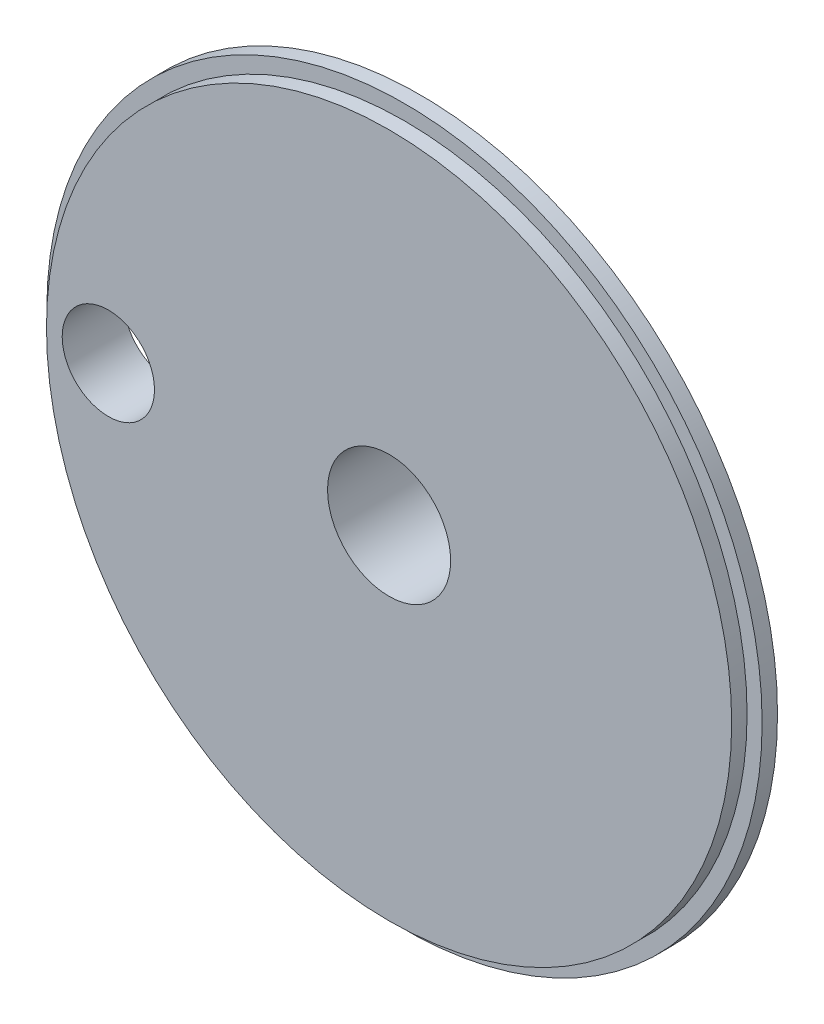
SolidWorks part; units mm, degrees
ref_plane "Front Plane" through (0, 0, 0) normal (0, 0, 1) x (1, 0, 0)
ref_plane "Top Plane" through (0, 0, 0) normal (0, 1, 0) x (1, 0, 0)
ref_plane "Right Plane" through (0, 0, 0) normal (1, 0, 0) x (0, 0, -1)
sketch "Sketch7" plane through (0, 0, 0) normal (0, 0, 1) x (1, 0, 0)
  circle A0 centre (0, 0) radius 46.5
  circle A2 centre (0, 0) radius 8
  circle A3 centre (-36.5, 0) radius 6
  dimension "D1" = 16
  dimension "D2" = 12
  dimension "D3" = 93
  dimension "D4" = 36.5
extrude "Boss-Extrude9" add sketch "Sketch7" along normal blind 2
sketch "Sketch8" plane through (0, 0, 2) normal (0, 0, 1) x (1, 0, 0)
  circle A0 centre (0, 0) radius 44.5424
  circle A1 centre (0, 0) radius 8 construction
  circle A2 centre (-36.5, 0) radius 6 construction
  circle A3 centre (0, 0) radius 8
  circle A4 centre (-36.5, 0) radius 6
extrude "Boss-Extrude10" add sketch "Sketch8" along normal blind 2
sketch "Sketch9" plane through (0, 0, 0) normal (0, 0, -1) x (-1, 0, 0)
  circle A0 centre (0, 0) radius 10
  circle A1 centre (36.5, 0) radius 8
  circle M2 centre (0, 0) radius 8
  circle M3 centre (36.5, 0) radius 6
  dimension "D1" = 16
  dimension "D2" = 20
extrude "Boss-Extrude11" add sketch "Sketch9" along normal blind 8 contours A0 M2 region at (9.7172, 0, 0)
extrude "Boss-Extrude12" add sketch "Sketch9<3>" along normal blind 4 contours A1 M3 region at (-28.7263, 0, 0)
sketch "Sketch9<3>" plane through (0, 0, 0) normal (0, 0, -1) x (-1, 0, 0) same geometry as "Sketch9"
